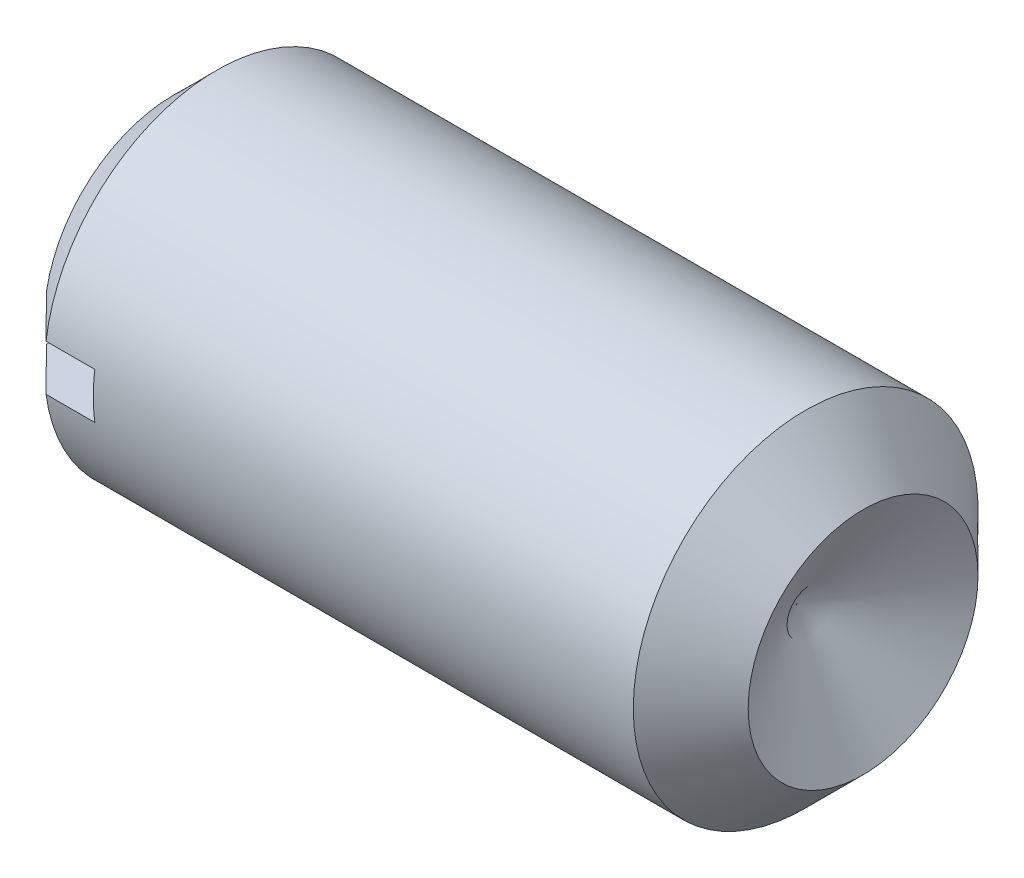
SolidWorks part; units mm, degrees
ref_plane "Front" through (0, 0, 0) normal (0, 0, 1) x (1, 0, 0)
ref_plane "Top" through (0, 0, 0) normal (0, 1, 0) x (1, 0, 0)
ref_plane "Right" through (0, 0, 0) normal (1, 0, 0) x (0, 0, -1)
sketch "Sketch1" plane through (0, 0, 0) normal (0, 0, 1) x (1, 0, 0)
  line L0 (0, 0) -> (5.4226, 0)
  line L2 (6, 1) -> (5.5, 1.5)
  line L3 (5.5, 1.5) -> (0.375, 1.5)
  line L4 (0.375, 1.5) -> (0, 1.125)
  line L5 (0, 1.125) -> (0, 0)
  line L6 (-10.745, 0) -> (0.8952, 0) construction
  line L7 (6, 1) -> (5.4226, 0)
  dimension "D2" = 45
  dimension "D1" = 45
  dimension "l" = 6
  dimension "D3" = 60
revolve "Base" add sketch "Sketch1" angle 360 about L6
cosmetic thread "ThreadCosmetic1" [suppressed] parameters "D2"=2.25
sketch "Sketch2" plane through (0, 0, 0) normal (0, 0, 1) x (1, 0, 0)
  line L1 (0, 0.2) -> (0.8, 0.2)
  line L2 (0, 0.2) -> (0, -0.2)
  line L3 (0, -0.2) -> (0.8, -0.2)
  line L4 (0.8, 0.2) -> (0.8, -0.2)
  line L5 (0, 1.125) -> (0, -1.125) construction
  dimension "m" = 0.2
extrude "Notch" cut sketch "Sketch2" against normal through all and the other way through all
sketch "Sketch3" plane through (0, 0, 0) normal (0, 0, 1) x (1, 0, 0)
  line L0 (0.375, 1.1752) -> (0.5625, 1.5)
  line L1 (0.5625, 1.5) -> (0.5625, 1.875)
  line L2 (0.5625, 1.875) -> (0.1875, 1.875)
  line L3 (0.1875, 1.875) -> (0.1875, 1.5)
  line L4 (0.1875, 1.5) -> (0.375, 1.1752)
  line L5 (0.375, 1.5) -> (0.375, 0.2) construction
  line L6 (0, 0) -> (3.2886, 0) construction
  dimension "D1" = 3
  dimension "D2" = 0.375
revolve "Cut-Revolve10" [suppressed] cut sketch "Sketch3" angle 360 about L6
pattern_linear "LPattern10" [suppressed] count 13 spacing 0.45 along (1, 0, 0) of bodies 103
equation "\"df@Sketch1\" = \"D2@ThreadCosmetic1\""
equation "\"m@Sketch2\" = \"n@Sketch2\" / 2"
equation "\"D1@Sketch3\" = \"d@Sketch1\""
equation "\"D2@Sketch3\" =  ( \"d@Sketch1\" - \"D2@ThreadCosmetic1\" )  / 2"
equation "\"D3@LPattern10\" = \"D2@Sketch3\" * 1.2"
equation "\"D1@LPattern10\" =  ( \"l@Sketch1\" -  ( \"d@Sketch1\" - \"df@Sketch1\" )  / 2 )  / \"D3@LPattern10\""
